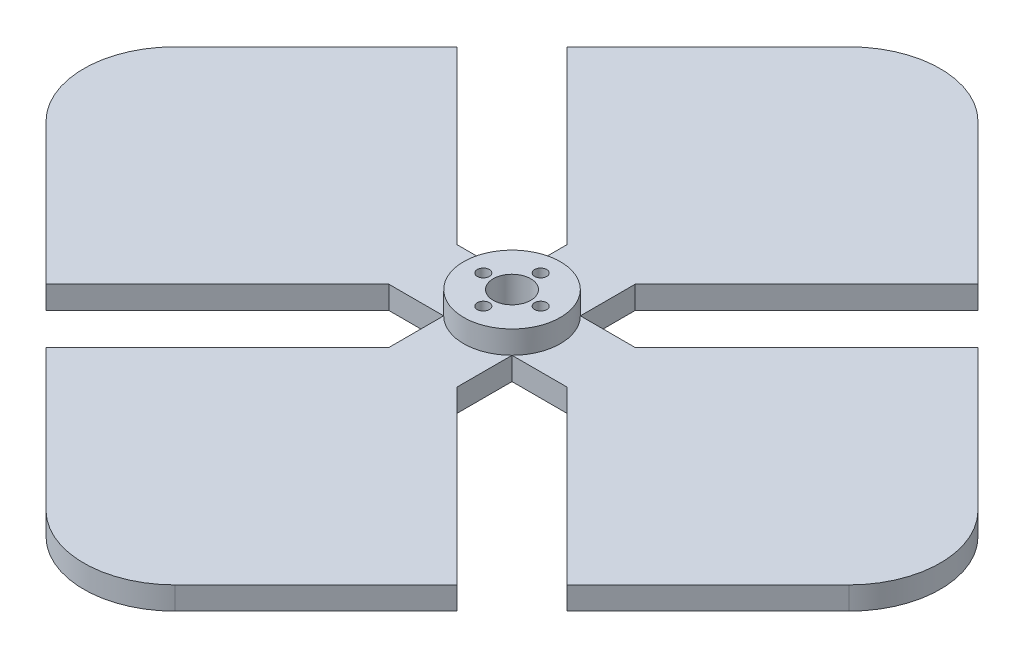
SolidWorks part; units mm, degrees
ref_plane "Front Plane" through (0, 0, 0) normal (0, 0, 1) x (1, 0, 0)
ref_plane "Top Plane" through (0, 0, 0) normal (0, 1, 0) x (1, 0, 0)
ref_plane "Right Plane" through (0, 0, 0) normal (1, 0, 0) x (0, 0, -1)
sketch "Sketch4" plane through (0, 0, 0) normal (0, 1, 0) x (1, 0, 0)
  line L8 (15.3035, 0) -> (72.5975, -57.294)
  line L9 (15.3035, 0) -> (72.5975, 57.294)
  line L10 (72.5975, -57.294) -> (129.8916, 0)
  line L11 (72.5975, 57.294) -> (129.8916, 0)
  line L13 (0, 9.525) -> (24.8285, 9.525)
  line L14 (0, 9.525) -> (0, -9.525)
  line L15 (0, -9.525) -> (24.8285, -9.525)
  line L16 (24.8285, 9.525) -> (24.8285, -9.525)
  dimension "D1" = 81.026
  dimension "D2" = 15.3035
  dimension "D3" = 19.05
extrude "Boss-Extrude5" add sketch "Sketch4" along normal blind 6.35 contours L9 L16 L8 L10 L11 | L16 L9 L8 | L14 L15 L8 L9 L13 region at (21.6535, 0, 0) region at (10.2214, 0, 0) region at (73.3114, 0, 0)
sketch "Sketch6" plane through (0, 0, 0) normal (0, 0, 1) x (1, 0, 0)
  line L0 (0, 0) -> (0, 27.64) construction
fillet "Fillet1" radius 25.4 1 edges at (129.8916, 3.175, 0)
pattern_circular "CirPattern7" count 4 over 360 about axis through (0, 0, 0) along (0, 1, 0) of "Boss-Extrude5", "Fillet1"
sketch "Sketch13" plane through (0, 6.35, 0) normal (0, 1, 0) x (1, 0, 0)
  circle A0 centre (0, 0) radius 13.4704
extrude "Boss-Extrude8" add sketch "Sketch13" along normal blind 6.35
sketch "Sketch1" plane through (0, 0, 0) normal (0, 1, 0) x (1, 0, 0)
  circle A0 centre (0, 0) radius 2.6905 construction
  circle A1 centre (0, 0) radius 5.227
  circle A2 centre (8, 0) radius 1.6865
  circle A6 centre (0, -8) radius 1.6865
  circle A7 centre (-8, 0) radius 1.6865
  circle A8 centre (0, 8) radius 1.6865
  point P15 (0, 0)
  dimension "D1" = 10.454
  dimension "D3" = 3.373
  dimension "D2" = 8
extrude "Cut-Extrude1" cut sketch "Sketch1" along normal through all
equation "\"tightTol\" = 0.005in"
equation "\"normTol\" = 0.01in"
equation "\"looseTol\" = 0.02in"
equation "\"D1@Sketch1\"=\"normTol\"+10.2mm"
equation "\"D2@Sketch1\"=8mm"
equation "\"D1@Sketch4\"=3.25-3*\"looseTol\""
equation "\"D2@Sketch4\"=9/16+2*\"looseTol\""
equation "\"D3@Sketch1\"=3.5mm-\"tightTol\""
